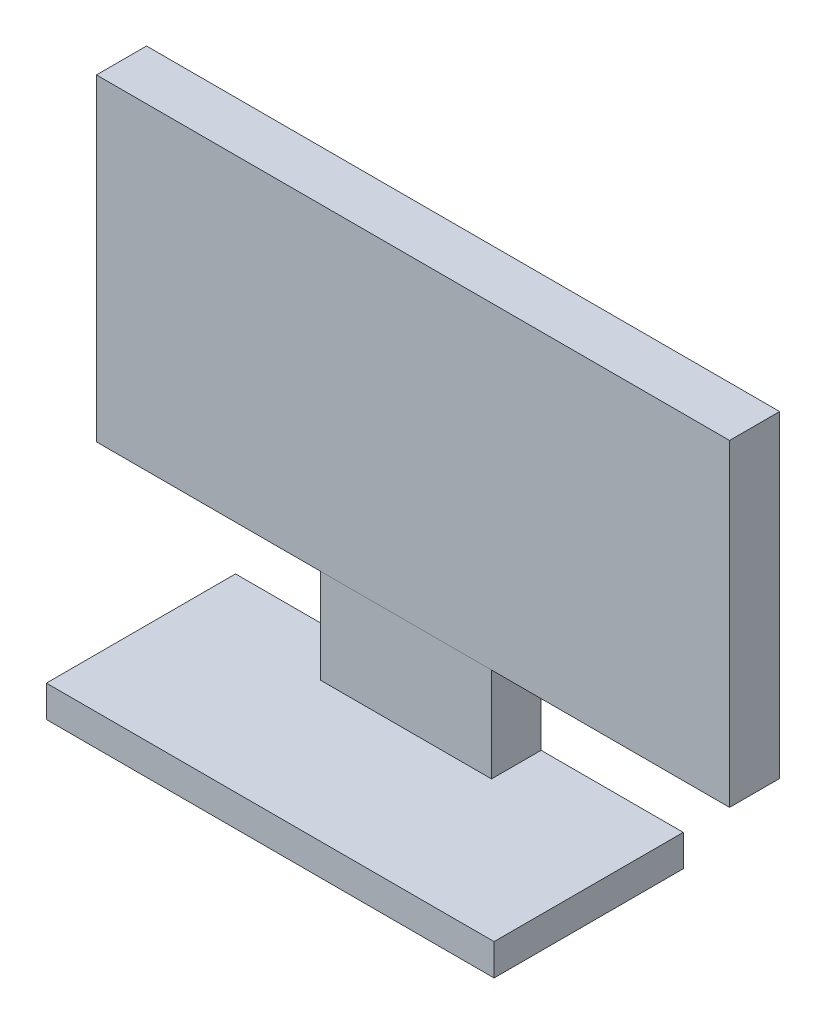
SolidWorks part; units mm, degrees
ref_plane "Front Plane" through (0, 0, 0) normal (0, 0, 1) x (1, 0, 0)
ref_plane "Top Plane" through (0, 0, 0) normal (0, 1, 0) x (1, 0, 0)
ref_plane "Right Plane" through (0, 0, 0) normal (1, 0, 0) x (0, 0, -1)
sketch "Sketch1" plane through (0, 0, 0) normal (0, 1, 0) x (1, 0, 0)
  line L0 (14.5041, 9.9599) -> (50.0041, 9.9599)
  line L5 (14.5041, 21.2754) -> (50.0041, 21.2754)
  line L10 (14.5041, 21.2754) -> (14.5041, 6.2754)
  line L11 (14.5041, 6.2754) -> (50.0041, 6.2754)
  line L12 (50.0041, 21.2754) -> (50.0041, 6.2754)
  line L13 (14.5041, 14.0701) -> (50.0041, 14.1179)
  dimension "D1" = 35.5
  dimension "D2" = 15
extrude "Boss-Extrude7" add sketch "Sketch1" along normal blind 2.5 contours L13 L12 L5 L10 | L13 L10 L0 L12 | L0 L10 L11 L12 region at (32.2883, 0, -12.0269) region at (32.2541, 0, -8.1176) region at (32.2344, 0, -17.6847)
sketch "Sketch5" plane through (0, 2.5, 0) normal (0, 1, 0) x (1, 0, 0)
  line L0 (14.5041, 21.2754) -> (50.0041, 21.2754) construction
  line L1 (25.1665, 21.2754) -> (38.7336, 21.2754)
  line L2 (25.1665, 21.2754) -> (25.1665, 17.3426)
  line L3 (25.1665, 17.3426) -> (38.7336, 17.3426)
  line L4 (38.7336, 21.2754) -> (38.7336, 17.3426)
extrude "Boss-Extrude8" add sketch "Sketch5" along normal blind 7.5
sketch "Sketch6" plane through (1.1246, 10, 0) normal (0, 1, 0) x (1, 0, 0)
  line L2 (6.3022, 21.2948) -> (56.5022, 21.2948)
  line L3 (6.3022, 21.2948) -> (6.3022, 17.3248)
  line L4 (6.3022, 17.3248) -> (56.5022, 17.3248)
  line L5 (56.5022, 21.2948) -> (56.5022, 17.3248)
  dimension "D1" = 50.2
  dimension "D2" = 3.97
extrude "Boss-Extrude9" add sketch "Sketch6" along normal blind 25.2 contours L3 L2 L5 L4
